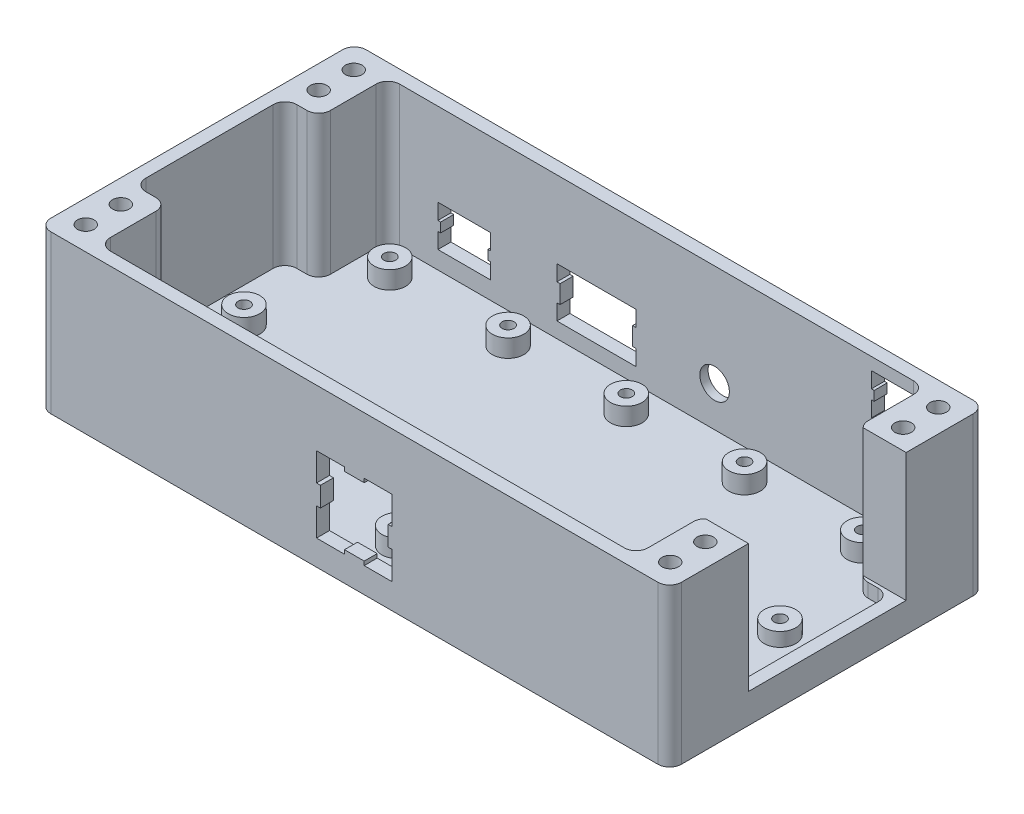
SolidWorks part; units mm, degrees
ref_plane "Спереди" through (0, 0, 0) normal (0, 0, 1) x (1, 0, 0)
ref_plane "Сверху" through (0, 0, 0) normal (0, 1, 0) x (1, 0, 0)
ref_plane "Справа" through (0, 0, 0) normal (1, 0, 0) x (0, 0, -1)
sketch "Эскиз1" plane through (0, 0, 0) normal (0, 1, 0) x (1, 0, 0)
  line L1 (-77, -40) -> (77, -40)
  line L2 (-80, -37) -> (-80, 37)
  line L3 (-77, 40) -> (77, 40)
  line L4 (80, -37) -> (80, 37)
  line L5 (-80, -40) -> (80, 40) construction
  line L6 (-80, 40) -> (80, -40) construction
  arc A0 (-77, -40) -> (-80, -37) centre (-77, -37) cw
  arc A1 (-80, 37) -> (-77, 40) centre (-77, 37) cw
  arc A2 (77, 40) -> (80, 37) centre (77, 37) cw
  arc A3 (77, -40) -> (80, -37) centre (77, -37) ccw
  point P0 (0, 0)
  dimension "D3" = 3
  dimension "D1" = 160
  dimension "D2" = 80
extrude "Бобышка-Вытянуть1" add sketch "Эскиз1" along normal blind 40
sketch "Эскиз2" plane through (0, 40, 0) normal (0, 1, 0) x (1, 0, 0)
  line L1 (-75.75, -36.7) -> (75.75, -36.7)
  line L2 (-76.75, -35.7) -> (-76.75, 35.7)
  line L3 (-75.75, 36.7) -> (75.75, 36.7)
  line L4 (76.75, -35.7) -> (76.75, 35.7)
  line L5 (-76.75, -36.7) -> (76.75, 36.7) construction
  line L6 (-76.75, 36.7) -> (76.75, -36.7) construction
  arc A0 (-75.75, -36.7) -> (-76.75, -35.7) centre (-75.75, -35.7) cw
  arc A1 (75.75, -36.7) -> (76.75, -35.7) centre (75.75, -35.7) ccw
  arc A2 (75.75, 36.7) -> (76.75, 35.7) centre (75.75, 35.7) cw
  arc A3 (-76.75, 35.7) -> (-75.75, 36.7) centre (-75.75, 35.7) cw
  point P0 (0, 0)
  dimension "D3" = 1
  dimension "D1" = 153.5
  dimension "D2" = 73.4
extrude "Вырез-Вытянуть1" cut sketch "Эскиз2" against normal blind 36
sketch "Эскиз3" plane through (0, 4, 0) normal (0, 1, 0) x (1, 0, 0)
  line L0 (-76.75, 35.7) -> (-76.75, -35.7) construction
  line L1 (-76.75, -36.7) -> (-68.2, -36.7)
  line L2 (-76.75, -36.7) -> (-76.75, -19.15)
  line L3 (-76.75, -19.15) -> (-71.2, -19.15)
  line L4 (-68.2, -36.7) -> (-68.2, -22.15)
  line L5 (-75.75, -36.7) -> (75.75, -36.7) construction
  line L6 (0, 0) -> (-76.75, 0) construction
  line L7 (-76.75, 35.7) -> (-76.75, -35.7) construction
  line L8 (0, 0) -> (0, -36.7) construction
  line L9 (-68.2, 36.7) -> (-68.2, 22.15)
  line L10 (-76.75, 19.15) -> (-71.2, 19.15)
  line L11 (-76.75, 36.7) -> (-76.75, 19.15)
  line L12 (-76.75, 36.7) -> (-68.2, 36.7)
  line L13 (76.75, 36.7) -> (68.2, 36.7)
  line L14 (76.75, 36.7) -> (76.75, 19.15)
  line L15 (76.75, 19.15) -> (71.2, 19.15)
  line L16 (68.2, 36.7) -> (68.2, 22.15)
  line L17 (68.2, -36.7) -> (68.2, -22.15)
  line L18 (76.75, -19.15) -> (71.2, -19.15)
  line L19 (76.75, -36.7) -> (76.75, -19.15)
  line L20 (76.75, -36.7) -> (68.2, -36.7)
  arc A0 (68.2, -22.15) -> (71.2, -19.15) centre (71.2, -22.15) cw
  arc A1 (71.2, 19.15) -> (68.2, 22.15) centre (71.2, 22.15) cw
  arc A2 (-68.2, 22.15) -> (-71.2, 19.15) centre (-71.2, 22.15) cw
  arc A3 (-71.2, -19.15) -> (-68.2, -22.15) centre (-71.2, -22.15) cw
  point P29 (68.2, -19.15)
  point P32 (68.2, 19.15)
  point P35 (-68.2, 19.15)
  point P38 (-68.2, -19.15)
  dimension "D3" = 3
  dimension "D1" = 38.3
  dimension "D2" = 136.4
extrude "Бобышка-Вытянуть2" add sketch "Эскиз3" along normal blind 36
sketch "Эскиз4" plane through (0, 40, 0) normal (0, 1, 0) x (1, 0, 0)
  line L0 (0, 0) -> (-76.75, 0) construction
  line L1 (-76.75, 19.15) -> (-76.75, -19.15) construction
  line L2 (0, 0) -> (0, -36.7) construction
  line L3 (-68.2, -36.7) -> (68.2, -36.7) construction
  circle A0 centre (-74.15, -34) radius 2.1
  circle A2 centre (-74.15, 34) radius 2.1
  circle A3 centre (74.15, 34) radius 2.1
  circle A4 centre (74.15, -34) radius 2.1
  circle A5 centre (-74.15, -25.1) radius 2.1
  circle A6 centre (-74.15, 25.1) radius 2.1
  circle A7 centre (74.15, 25.1) radius 2.1
  circle A8 centre (74.15, -25.1) radius 2.1
  dimension "D3" = 4.2
  dimension "D1" = 68
  dimension "D2" = 148.3
  dimension "D4" = 50.2
extrude "Вырез-Вытянуть2" cut sketch "Эскиз4" against normal through all
sketch "Эскиз5" plane through (0, 4, 0) normal (0, 1, 0) x (1, 0, 0)
  line L0 (0, 0) -> (-76.75, 0) construction
  line L1 (-76.75, 19.15) -> (-76.75, -19.15) construction
  circle A0 centre (0, -29) radius 4
  circle A1 centre (0, 29) radius 4
  circle A2 centre (0, 29) radius 1.5
  circle A3 centre (0, -29) radius 1.5
  dimension "D1" = 8
  dimension "D3" = 3
  dimension "D2" = 58
extrude "Бобышка-Вытянуть3" add sketch "Эскиз5" along normal blind 4.5
pattern_linear "Линейный массив1" count 3 spacing 30 along (1, 0, 0) count 3 spacing 30 along (-1, 0, 0) of "Бобышка-Вытянуть3"
sketch "Эскиз6" plane through (0, 4, 0) normal (0, 1, 0) x (1, 0, 0)
  line L0 (0, 0) -> (0, 36.7) construction
  line L1 (68.2, 36.7) -> (-68.2, 36.7) construction
  circle A0 centre (-68, 0) radius 4
  circle A1 centre (-68, 0) radius 1.5
  circle A2 centre (-60, 29) radius 4 construction
  circle A3 centre (-60, 29) radius 1.5 construction
  circle A4 centre (68, 0) radius 1.5
  circle A5 centre (68, 0) radius 4
  dimension "D1" = 136
extrude "Бобышка-Вытянуть4" add sketch "Эскиз6" along normal blind 4.5
fillet "Скругление1" radius 3 8 edges at (76.75, 22, 19.15) (68.2, 22, 36.7) (76.75, 22, -19.15) (68.2, 22, -36.7) (-68.2, 22, 36.7) (-76.75, 22, 19.15) (-76.75, 22, -19.15) (-68.2, 22, -36.7)
sketch "Эскиз7" plane through (80, 0, 0) normal (1, 0, 0) x (0, 0, -1)
  line L0 (-37, 0) -> (37, 0) construction
  line L1 (-20, 47.5) -> (20, 47.5)
  line L2 (-20, 47.5) -> (-20, 7.5)
  line L3 (-20, 7.5) -> (20, 7.5)
  line L4 (20, 47.5) -> (20, 7.5)
  line L5 (-20, 47.5) -> (20, 7.5) construction
  line L6 (-20, 7.5) -> (20, 47.5) construction
  point P0 (0, 27.5)
  dimension "D1" = 40
  dimension "D2" = 7.5
extrude "Вырез-Вытянуть3" cut sketch "Эскиз7" against normal blind 25
sketch "Эскиз8" plane through (0, 0, -40) normal (0, 0, -1) x (-1, 0, 0)
  line L0 (-54.5, 18.9) -> (-67.9, 18.9)
  line L5 (55.5, 18.9) -> (42.1, 18.9)
  line L6 (42.8, 14.9) -> (42.8, 12.5)
  line L10 (-67.2, 14.9) -> (-67.2, 12.5)
  line L12 (-54.5, 14.9) -> (-55.2, 14.9)
  line L17 (55.5, 14.9) -> (54.8, 14.9)
  line L18 (42.1, 18.9) -> (42.1, 14.9)
  line L19 (-67.9, 18.9) -> (-67.9, 14.9)
  line L20 (-67.9, 14.9) -> (-67.2, 14.9)
  line L21 (-61.2, 8.5) -> (-61.2, 18.9) construction
  line L22 (-61.2, 18.9) -> (-61.2, 8.5) construction
  line L23 (-61.2, 13.7) -> (-67.2, 13.7) construction
  line L24 (-54.5, 18.9) -> (-54.5, 14.9)
  line L25 (-55.2, 14.9) -> (-55.2, 12.5)
  line L26 (-54.5, 8.5) -> (-54.5, 12.5)
  line L27 (-67.9, 12.5) -> (-67.2, 12.5)
  line L28 (-67.9, 8.5) -> (-67.9, 12.5)
  line L29 (-54.5, 12.5) -> (-55.2, 12.5)
  line L30 (-54.5, 8.5) -> (-67.9, 8.5)
  line L31 (42.1, 14.9) -> (42.8, 14.9)
  line L32 (55.5, 18.9) -> (55.5, 14.9)
  line L33 (54.8, 14.9) -> (54.8, 12.5)
  line L34 (55.5, 8.5) -> (55.5, 12.5)
  line L35 (42.1, 12.5) -> (42.8, 12.5)
  line L36 (42.1, 8.5) -> (42.1, 12.5)
  line L37 (55.5, 12.5) -> (54.8, 12.5)
  line L38 (55.5, 8.5) -> (42.1, 8.5)
  line L39 (48.8, 18.9) -> (48.8, 8.5) construction
  line L40 (48.8, 13.7) -> (42.8, 13.7) construction
  line L41 (-54.5, 36.9) -> (-67.9, 36.9)
  line L42 (-67.2, 32.9) -> (-67.2, 30.5)
  line L43 (-54.5, 32.9) -> (-55.2, 32.9)
  line L44 (-67.9, 36.9) -> (-67.9, 32.9)
  line L45 (-67.9, 32.9) -> (-67.2, 32.9)
  line L46 (-54.5, 36.9) -> (-54.5, 32.9)
  line L47 (-55.2, 32.9) -> (-55.2, 30.5)
  line L48 (-54.5, 26.5) -> (-54.5, 30.5)
  line L49 (-67.9, 30.5) -> (-67.2, 30.5)
  line L50 (-67.9, 26.5) -> (-67.9, 30.5)
  line L51 (-54.5, 30.5) -> (-55.2, 30.5)
  line L52 (-54.5, 26.5) -> (-67.9, 26.5)
  line L53 (-61.2, 26.5) -> (-61.2, 36.9) construction
  line L54 (-61.2, 36.9) -> (-61.2, 26.5) construction
  line L55 (-61.2, 31.7) -> (-67.2, 31.7) construction
  point P1 (48.8, 13.7)
  point P7 (-61.2, 13.7)
  point P31 (-55.2, 13.7)
  point P38 (54.8, 13.7)
  point P43 (-61.2, 31.7)
  point P56 (-55.2, 31.7)
  dimension "D1" = 4
  dimension "D2" = 6.7
  dimension "D3" = 1.2
  dimension "D4" = 6
  dimension "D5" = 2
  dimension "D6" = 110
  dimension "D8" = 18
  dimension "D7" = 2
extrude "Вырез-Вытянуть4" cut sketch "Эскиз8" against normal blind 10
ref_axis "Ось1" through (80, 18.9, -40) along (0, -1, 0)
ref_point "Точка1"
sketch "Эскиз9" plane through (0, 0, -40) normal (0, 0, -1) x (-1, 0, 0)
  line L0 (15.3, 14.2) -> (15.3, 20.5) construction
  line L1 (24.5, 20.5) -> (6.1, 20.5) construction
  line L2 (15.3, 14.2) -> (24.5, 14.2) construction
  line L3 (24.5, 7.9) -> (24.5, 20.5) construction
  line L4 (5.3, 20.5) -> (25.3, 20.5)
  line L5 (25.3, 7.2) -> (25.3, 21.2) construction
  line L6 (25.3, 20.5) -> (25.3, 16.5)
  line L7 (25.3, 16.5) -> (24.5, 16.5)
  line L8 (24.5, 16.5) -> (24.5, 11.9)
  line L9 (6.1, 16.5) -> (6.1, 11.9)
  line L10 (5.3, 16.5) -> (6.1, 16.5)
  line L11 (5.3, 20.5) -> (5.3, 16.5)
  line L12 (5.3, 7.9) -> (5.3, 11.9)
  line L13 (5.3, 11.9) -> (6.1, 11.9)
  line L14 (25.3, 11.9) -> (24.5, 11.9)
  line L15 (25.3, 7.9) -> (25.3, 11.9)
  line L16 (5.3, 7.9) -> (25.3, 7.9)
  circle A0 centre (-14.7, 14.2) radius 3.75
  point P23 (6.1, 14.2)
  dimension "D2" = 7.5
  dimension "D1" = 4
extrude "Вырез-Вытянуть5" cut sketch "Эскиз9" against normal up to surface (3.3 mm away) up to face at (-48.8, 13.7, -36.7)
sketch "Эскиз10" plane through (0, 0, -40) normal (0, 0, -1) x (-1, 0, 0)
  circle A0 centre (-14.7, 14.2) radius 6
extrude "Вырез-Вытянуть6" cut sketch "Эскиз10" against normal blind 1.2
ref_point "Точка2"
ref_axis "Ось2" through (30, 8.5, 29) along (0, 1, 0)
sketch "Эскиз11" plane through (0, 0, 40) normal (0, 0, 1) x (1, 0, 0)
  line L0 (-9.6, 25.6) -> (-2.5, 25.6)
  line L5 (-2.5, 25.6) -> (-2.5, 24.6)
  line L6 (-2.5, 24.6) -> (2.5, 24.6)
  line L7 (2.5, 24.6) -> (2.5, 25.6)
  line L20 (2.5, 25.6) -> (9.6, 25.6)
  line L21 (9.6, 25.6) -> (9.6, 18.5)
  line L22 (9.6, 18.5) -> (8.6, 18.5)
  line L23 (8.6, 18.5) -> (8.6, 13.5)
  line L24 (8.6, 13.5) -> (9.6, 13.5)
  line L25 (9.6, 13.5) -> (9.6, 6.4)
  line L26 (9.6, 6.4) -> (2.5, 6.4)
  line L27 (2.5, 6.4) -> (2.5, 7.4)
  line L28 (2.5, 7.4) -> (-2.5, 7.4)
  line L29 (-2.5, 7.4) -> (-2.5, 6.4)
  line L30 (-2.5, 6.4) -> (-9.6, 6.4)
  line L31 (-9.6, 6.4) -> (-9.6, 13.5)
  line L32 (-9.6, 13.5) -> (-8.6, 13.5)
  line L33 (-8.6, 13.5) -> (-8.6, 18.5)
  line L34 (-8.6, 18.5) -> (-9.6, 18.5)
  line L35 (-9.6, 18.5) -> (-9.6, 25.6)
  line L36 (-8.6, 16) -> (8.6, 16) construction
  line L37 (0, 24.6) -> (0, 7.4) construction
  line L38 (-77, 0) -> (77, 0) construction
  line L39 (80, 40) -> (80, 0) construction
  dimension "D1" = 17.2
  dimension "D2" = 5
  dimension "D3" = 1
  dimension "D4" = 16
  dimension "D5" = 80
ref_point "Точка3"
extrude "Вырез-Вытянуть7" cut sketch "Эскиз11" against normal up to next
